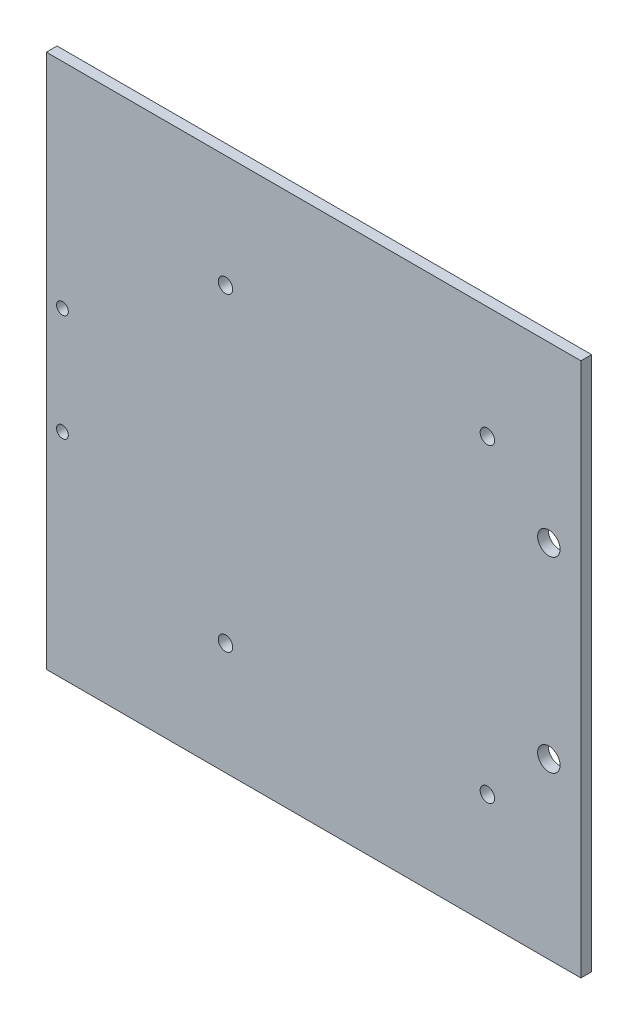
SolidWorks part; units mm, degrees
ref_plane "前视基准面" through (0, 0, 0) normal (0, 0, 1) x (1, 0, 0)
ref_plane "上视基准面" through (0, 0, 0) normal (0, 1, 0) x (1, 0, 0)
ref_plane "右视基准面" through (0, 0, 0) normal (1, 0, 0) x (0, 0, -1)
sketch "草图1" plane through (0, 0, 0) normal (0, 0, 1) x (1, 0, 0)
  line L0 (50, 0) -> (-50, 0) construction
  line L1 (-50, 50) -> (50, 50)
  line L2 (-50, 50) -> (-50, -50)
  line L3 (-50, -50) -> (50, -50)
  line L4 (50, 50) -> (50, -50)
  line L5 (-50, 50) -> (50, -50) construction
  line L6 (-50, -50) -> (50, 50) construction
  circle A0 centre (-47, 10) radius 1.1
  circle A1 centre (-47, -10) radius 1.1
  point P0 (0, 0)
  dimension "D3" = 2.2
  dimension "D4" = 20
  dimension "D5" = 3
  dimension "D1" = 100
  dimension "D2" = 100
extrude "凸台-拉伸1" add sketch "草图1" along normal blind 2
sketch "草图3" plane through (0, 0, 2) normal (0, 0, 1) x (1, 0, 0)
  line L0 (-50, 0) -> (50, 0) construction
  line L1 (-16.5, -50) -> (-16.5, 50) construction
  line L2 (8, -50) -> (8, 50) construction
  line L3 (32.5, -50) -> (32.5, 50) construction
  line L4 (50, -50) -> (50, 50)
  line L5 (50, 50) -> (-50, 50)
  line L6 (-50, 50) -> (-50, -50)
  line L7 (-50, -50) -> (50, -50)
  line L8 (50, -50) -> (50, 50)
  line L9 (50, 50) -> (-50, 50)
  line L10 (-50, 50) -> (-50, -50)
  line L11 (-50, -50) -> (50, -50)
  circle A0 centre (-16.5, -29) radius 1.35
  circle A1 centre (-16.5, 29) radius 1.35
  circle A2 centre (32.5, 29) radius 1.35
  circle A3 centre (32.5, -29) radius 1.35
  dimension "D3" = 2.7
  dimension "D4" = 58
  dimension "D5" = 49
  dimension "D2" = 33.5
  dimension "D1" = 0
extrude "切除-拉伸1" cut sketch "草图3" against normal through all contours A0 | A1 | A2 | A3 region at (-16.5, -29, 2) region at (-16.5, 29, 2) region at (32.5, 29, 2) region at (32.5, -29, 2)
sketch "草图7" plane through (0, 0, 2) normal (0, 0, 1) x (1, 0, 0)
  line L0 (50, 0) -> (-50, 0) construction
  line L1 (44, 50) -> (44, -50) construction
  line L4 (50, -50) -> (50, 50)
  line L5 (50, 50) -> (-50, 50)
  line L6 (-50, 50) -> (-50, -50)
  line L7 (-50, -50) -> (50, -50)
  line L8 (50, -50) -> (50, 50)
  line L9 (50, 50) -> (-50, 50)
  line L10 (-50, 50) -> (-50, -50)
  line L11 (-50, -50) -> (50, -50)
  circle A0 centre (44, 17.5) radius 2.1
  circle A1 centre (44, -17.5) radius 2.1
  dimension "D3" = 4.2
  dimension "D4" = 35
  dimension "D2" = 6
  dimension "D1" = 0
extrude "切除-拉伸5" cut sketch "草图7" against normal blind 10 contours A0 | A1 region at (44, 17.5, 2) region at (44, -17.5, 2)
